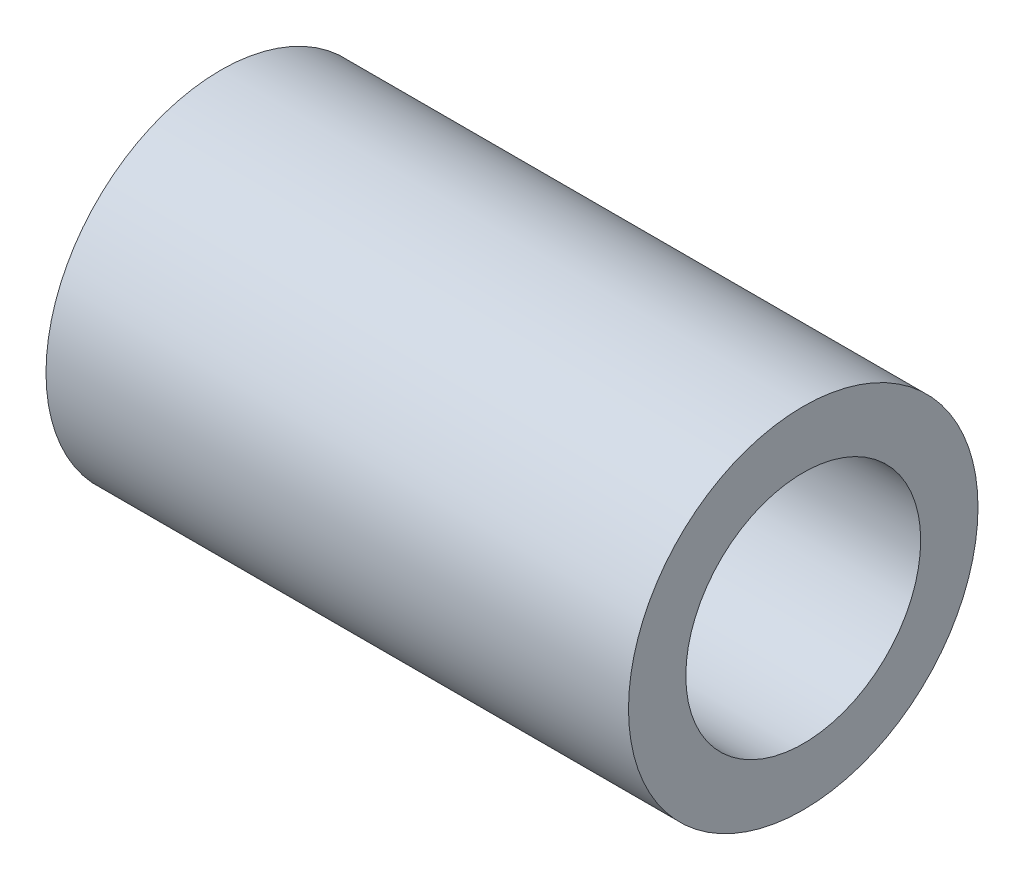
SolidWorks part; units mm, degrees
ref_plane "Front Plane" through (0, 0, 0) normal (0, 0, 1) x (1, 0, 0)
ref_plane "Top Plane" through (0, 0, 0) normal (0, 1, 0) x (1, 0, 0)
ref_plane "Right Plane" through (0, 0, 0) normal (1, 0, 0) x (0, 0, -1)
sketch "Sketch1" plane through (0, 0, 0) normal (1, 0, 0) x (0, 0, -1)
  circle A0 centre (0, 0) radius 4.7625
  dimension "D1" = 9.525
extrude "Boss-Extrude1" add sketch "Sketch1" along normal blind 15.875
sketch "Sketch2" plane through (0, 0, 0) normal (-1, 0, 0) x (0, 0, 1)
  circle A0 centre (0, 0) radius 3.2004
  dimension "D1" = 6.4008
extrude "Cut-Extrude1" cut sketch "Sketch2" against normal blind 15.875
